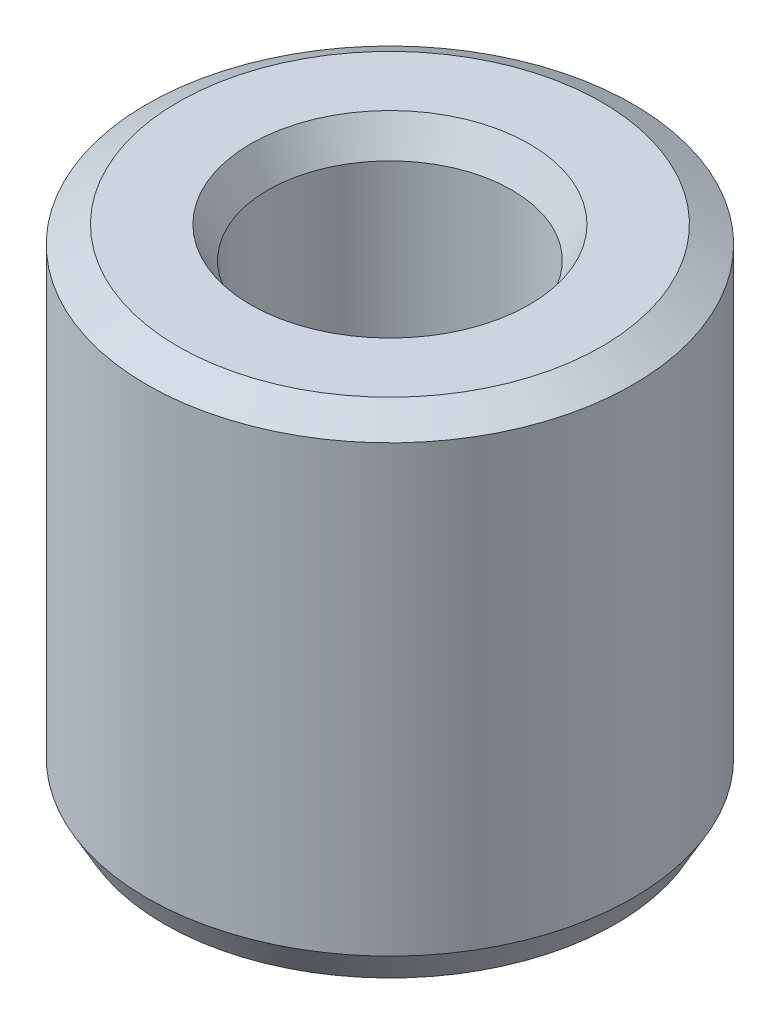
SolidWorks part; units mm, degrees
ref_plane "Front Plane" through (0, 0, 0) normal (0, 0, 1) x (1, 0, 0)
ref_plane "Top Plane" through (0, 0, 0) normal (0, 1, 0) x (1, 0, 0)
ref_plane "Right Plane" through (0, 0, 0) normal (1, 0, 0) x (0, 0, -1)
sketch "Sketch1" plane through (0, 0, 0) normal (0, 1, 0) x (1, 0, 0)
  circle A0 centre (0, 0) radius 50
  dimension "SLEEVE_OD" = 100
extrude "Boss-Extrude1" add sketch "Sketch1" along normal blind 101.4691
sketch "Sketch2" plane through (0, 0, 0) normal (0, 1, 0) x (1, 0, 0)
  circle A0 centre (0, 0) radius 25.0845
  dimension "BORE_D" = 50.1691
extrude "Cut-Extrude1" cut sketch "Sketch2" along normal through all
chamfer "Chamfer1" distance 3.5878 angle 60.837 4 edges at (0, 101.4691, 25.0845) (0, 0, 25.0845) (0, 0, 50) (0, 101.4691, 50) first distance on face at (0, 101.4691, 25.0845) first distance on face at (0, 0, 25.0845) first distance on face at (0, 101.4691, 50)
